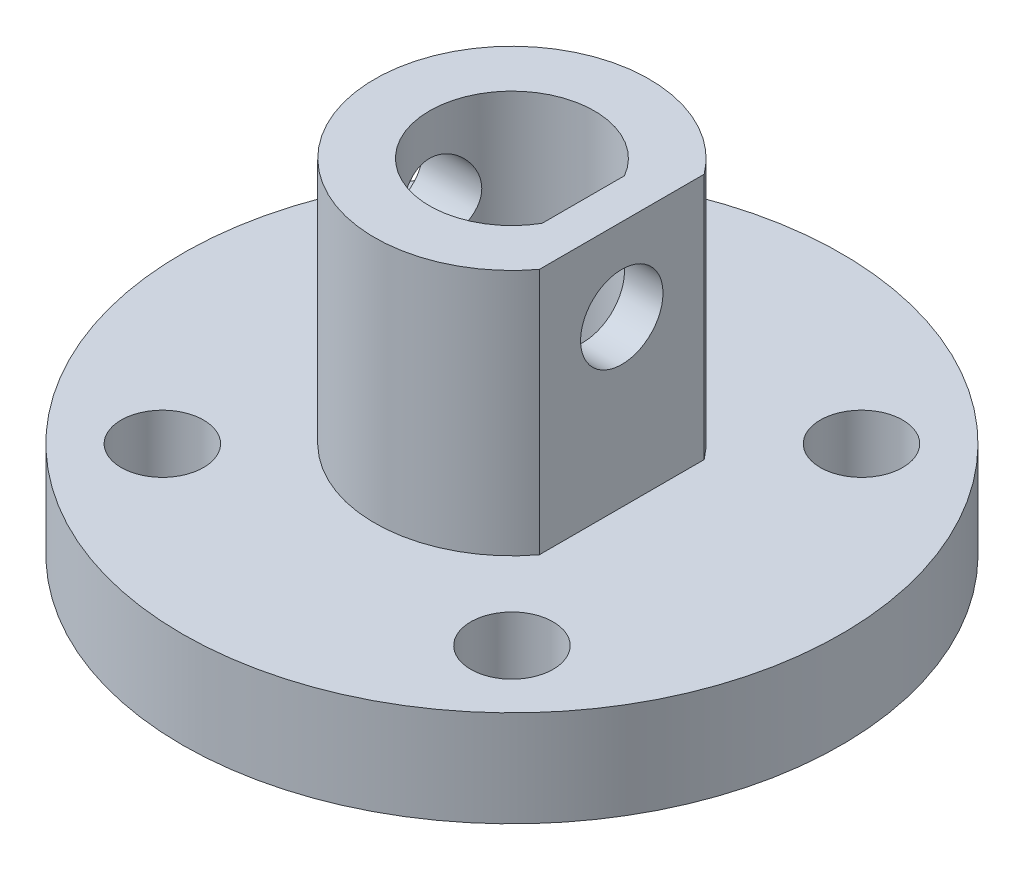
SolidWorks part; units mm, degrees
material "6061 Alloy"
ref_plane "前视基准面" through (0, 0, 0) normal (0, 0, 1) x (1, 0, 0)
ref_plane "上视基准面" through (0, 0, 0) normal (0, 1, 0) x (1, 0, 0)
ref_plane "右视基准面" through (0, 0, 0) normal (1, 0, 0) x (0, 0, -1)
sketch "Sketch1" plane through (0, 0, 0) normal (0, 1, 0) x (1, 0, 0)
  line L0 (0, 0) -> (6.364, 6.364)
  line L1 (2.5981, 1.5) -> (2.5981, -1.5)
  circle A0 centre (0, 0) radius 12
  circle A1 centre (6.364, 6.364) radius 1.5
  circle A2 centre (6.364, -6.364) radius 1.5
  circle A3 centre (-6.364, -6.364) radius 1.5
  circle A4 centre (-6.364, 6.364) radius 1.5
  circle A5 centre (0, 0) radius 3
  point P14 (0, 0)
  dimension "D1" = 24
  dimension "D3" = 3
  dimension "D5" = 6
  dimension "D2" = 9
  dimension "D6" = 3
  dimension "D4" = 4
extrude "Boss-Extrude1" add sketch "Sketch1" along normal blind 3.5 contours A0 A4 A3 A2 A1 | L1 A5 region at (2.7598, 0, 0) region at (-11.6606, 0, 0)
sketch "Sketch2" plane through (0, 3.5, 0) normal (0, 1, 0) x (1, 0, 0)
  line L0 (2.5981, 1.5) -> (2.5981, -1.5)
  line L1 (4, 3) -> (4, -3)
  circle A0 centre (0, 0) radius 5
  circle A1 centre (0, 0) radius 3
  dimension "D1" = 10
  dimension "D2" = 6
  dimension "D3" = 3
  dimension "D4" = 4
extrude "Boss-Extrude2" add sketch "Sketch2" along normal blind 9 contours L1 A0 A1 | L0 A1 region at (2.7598, 3.5, 0) region at (3.8655, 3.5, 0)
sketch "Sketch3" plane through (4, 0, 0) normal (1, 0, 0) x (0, 0, -1)
  line L0 (3, 12.5) -> (-3, 12.5) construction
  circle A0 centre (0, 9.5) radius 1.5
  dimension "D1" = 3
  dimension "D2" = 3
extrude "Cut-Extrude1" cut sketch "Sketch3" against normal blind 19
